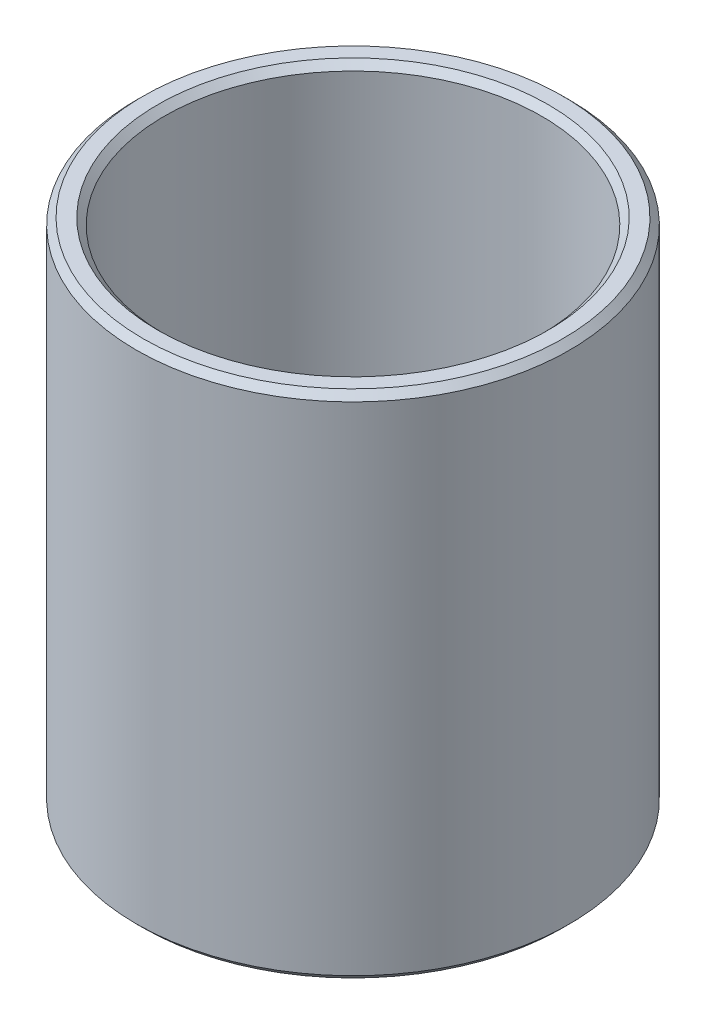
SolidWorks part; units mm, degrees
ref_plane "Front Plane" through (0, 0, 0) normal (0, 0, 1) x (1, 0, 0)
ref_plane "Top Plane" through (0, 0, 0) normal (0, 1, 0) x (1, 0, 0)
ref_plane "Right Plane" through (0, 0, 0) normal (1, 0, 0) x (0, 0, -1)
sketch "Sketch1" plane through (0, 0, 0) normal (0, 1, 0) x (1, 0, 0)
  circle A0 centre (0, 0) radius 37.5
  dimension "SLEEVE_OD" = 75
extrude "Boss-Extrude1" add sketch "Sketch1" along normal blind 88.3166
sketch "Sketch2" plane through (0, 0, 0) normal (0, 1, 0) x (1, 0, 0)
  circle A0 centre (0, 0) radius 32.6607
  dimension "BORE_D" = 65.3213
extrude "Cut-Extrude1" cut sketch "Sketch2" along normal through all
chamfer "Chamfer1" distance 1.1498 angle 45 4 edges at (0, 88.3166, 32.6607) (0, 0, 32.6607) (0, 0, 37.5) (0, 88.3166, 37.5)
